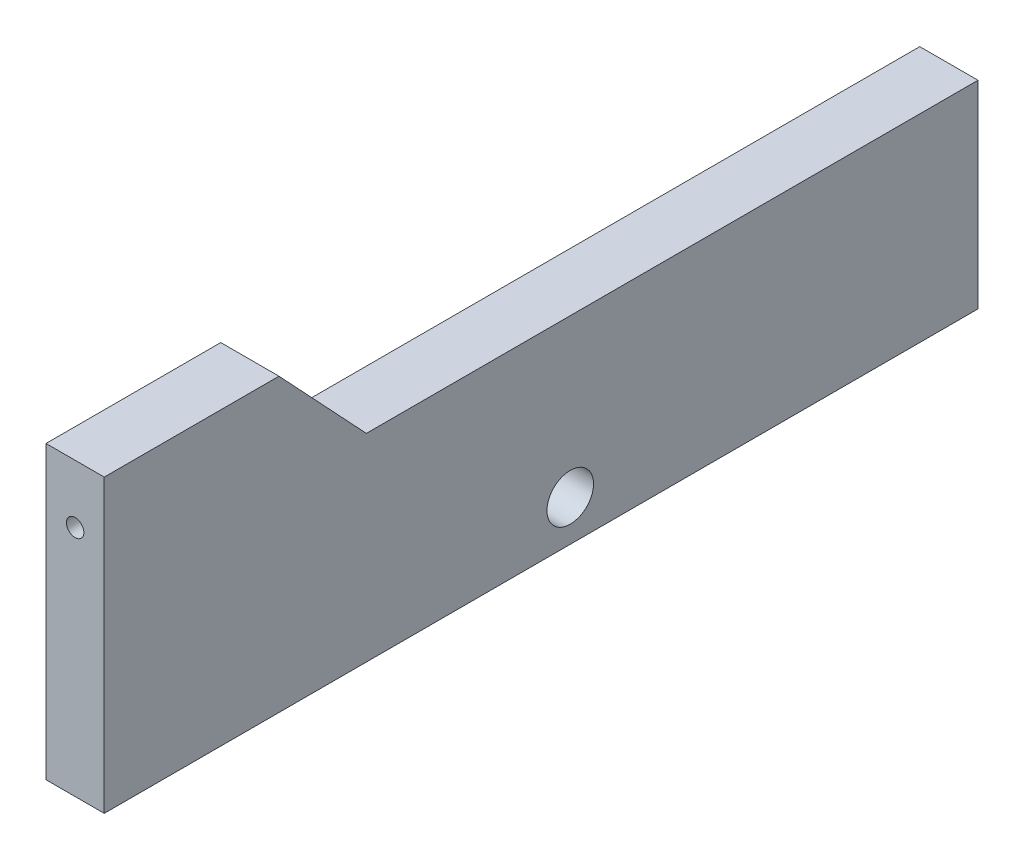
SolidWorks part; units mm, degrees
material "Perspex (TM) GS Acrylic Cast Sheet"
ref_plane "Front Plane" through (0, 0, 0) normal (0, 0, 1) x (1, 0, 0)
ref_plane "Top Plane" through (0, 0, 0) normal (0, 1, 0) x (1, 0, 0)
ref_plane "Right Plane" through (0, 0, 0) normal (1, 0, 0) x (0, 0, -1)
sketch "Sketch1" plane through (0, 0, 0) normal (1, 0, 0) x (0, 0, -1)
  line L0 (0, 0) -> (0, 50)
  line L1 (0, 5.5) -> (0, -5.5) construction
  line L2 (0, 50) -> (30, 50)
  line L3 (30, 50) -> (45, 34)
  line L4 (45, 34) -> (150, 34)
  line L5 (150, 34) -> (150, 0)
  line L6 (150, 0) -> (0, 0)
  dimension "D1" = 50
  dimension "D2" = 30
  dimension "D3" = 150
  dimension "D4" = 34
  dimension "D5" = 15
extrude "Boss-Extrude1" add sketch "Sketch1" along normal blind 10
sketch "Sketch2" plane through (10, 0, 0) normal (1, 0, 0) x (0, 0, -1)
  line L0 (0, 50) -> (0, 0) construction
  line L1 (140, 0) -> (-10, 0) construction
  circle A0 centre (80, 7) radius 4
  dimension "D2" = 7
  dimension "D3" = 8
  dimension "D1" = 80
extrude "Cut-Extrude1" cut sketch "Sketch2" against normal blind 10
sketch "Sketch3" plane through (0, 0, 0) normal (0, 0, 1) x (1, 0, 0)
  line L0 (10, 50) -> (0, 50) construction
  line L1 (10, 50) -> (10, 0) construction
  circle A0 centre (5, 40) radius 1.5
  dimension "D1" = 10
  dimension "D2" = 5
  dimension "D3" = 3
extrude "Cut-Extrude2" cut sketch "Sketch3" against normal blind 20
sketch "Sketch4" plane through (0, 0, 0) normal (0, -1, 0) x (1, 0, 0)
  line L0 (10, 0) -> (10, -150) construction
  line L1 (10, -150) -> (0, -150) construction
  circle A0 centre (5, -130) radius 1.5
  dimension "D1" = 3
  dimension "D2" = 5
  dimension "D3" = 20
extrude "Cut-Extrude3" cut sketch "Sketch4" against normal blind 20
